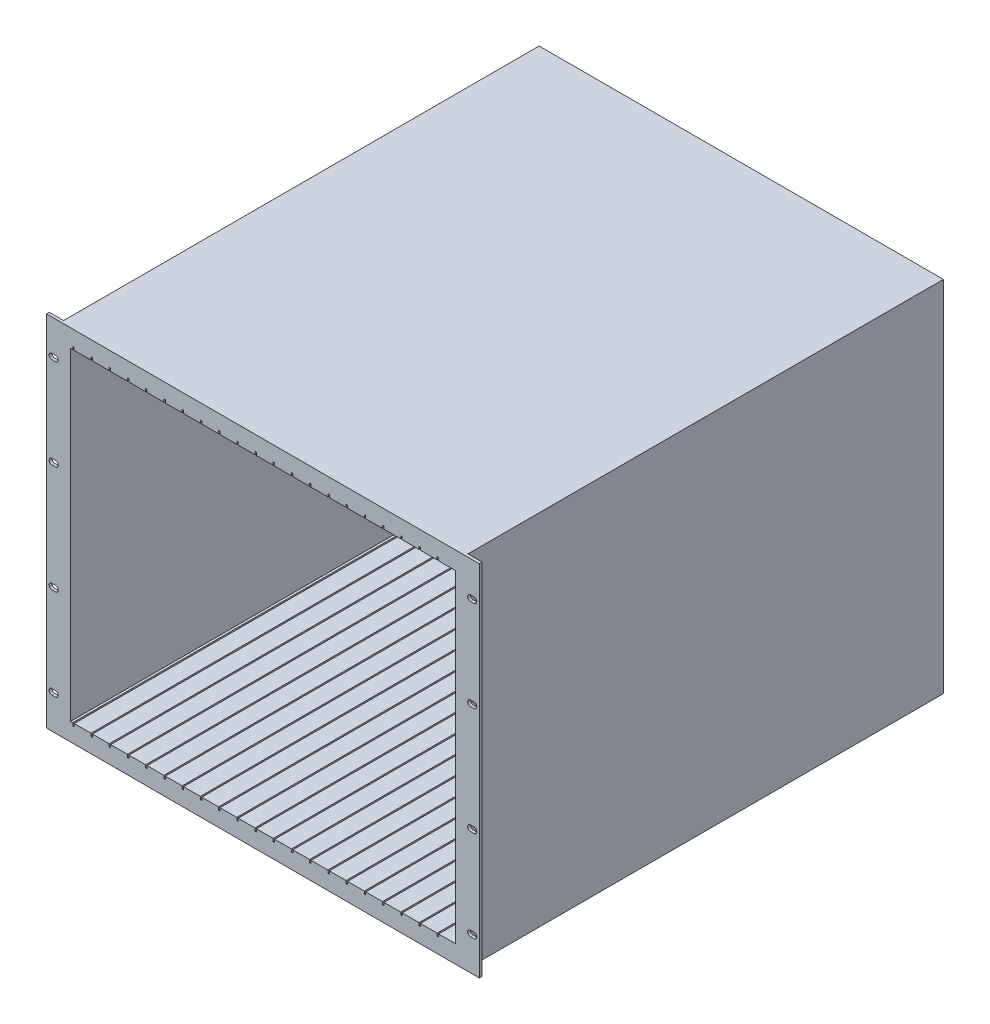
SolidWorks part; units mm, degrees
ref_plane "Front Plane" through (0, 0, 0) normal (0, 0, 1) x (1, 0, 0)
ref_plane "Top Plane" through (0, 0, 0) normal (0, 1, 0) x (1, 0, 0)
ref_plane "Right Plane" through (0, 0, 0) normal (1, 0, 0) x (0, 0, -1)
sketch "Sketch1" plane through (0, 0, 0) normal (0, 1, 0) x (1, 0, 0)
  line L1 (0, 0) -> (482.6, 0)
  line L2 (0, 0) -> (0, 533.4)
  line L3 (0, 533.4) -> (482.6, 533.4)
  line L4 (482.6, 0) -> (482.6, 533.4)
  dimension "D1" = 482.6
  dimension "D2" = 533.4
extrude "Boss-Extrude1" add sketch "Sketch1" along normal blind 19.8374
sketch "Sketch3" plane through (0, 19.8374, 0) normal (0, 1, 0) x (1, 0, 0)
  line L0 (0, 0) -> (482.6, 0) construction
  line L1 (0, 533.4) -> (26.67, 533.4)
  line L2 (0, 533.4) -> (0, 0)
  line L3 (0, 0) -> (26.67, 0)
  line L4 (26.67, 533.4) -> (26.67, 0)
  line L5 (482.6, 533.4) -> (0, 533.4) construction
  line L6 (455.93, 533.4) -> (482.6, 533.4)
  line L7 (455.93, 533.4) -> (455.93, 0)
  line L8 (455.93, 0) -> (482.6, 0)
  line L9 (482.6, 533.4) -> (482.6, 0)
  dimension "D1" = 26.67
  dimension "D2" = 26.67
extrude "Boss-Extrude2" add sketch "Sketch3" along normal blind 180.1876
sketch "Sketch2" plane through (0, 19.8374, 0) normal (0, 1, 0) x (1, 0, 0)
  line L0 (455.93, 533.4) -> (26.67, 533.4) construction
  line L1 (29.21, 533.4) -> (30.7975, 533.4)
  line L2 (29.21, 533.4) -> (29.21, 0)
  line L3 (29.21, 0) -> (30.7975, 0)
  line L4 (30.7975, 533.4) -> (30.7975, 0)
  line L5 (26.67, 0) -> (455.93, 0) construction
  line L6 (49.53, 533.4) -> (51.1175, 533.4)
  line L7 (49.53, 533.4) -> (49.53, 0)
  line L8 (49.53, 0) -> (51.1175, 0)
  line L9 (51.1175, 533.4) -> (51.1175, 0)
  line L10 (69.85, 533.4) -> (71.4375, 533.4)
  line L11 (69.85, 533.4) -> (69.85, 0)
  line L12 (69.85, 0) -> (71.4375, 0)
  line L13 (71.4375, 533.4) -> (71.4375, 0)
  line L14 (90.17, 533.4) -> (91.7575, 533.4)
  line L15 (90.17, 533.4) -> (90.17, 0)
  line L16 (90.17, 0) -> (91.7575, 0)
  line L17 (91.7575, 533.4) -> (91.7575, 0)
  line L18 (110.49, 533.4) -> (112.0775, 533.4)
  line L19 (110.49, 533.4) -> (110.49, 0)
  line L20 (110.49, 0) -> (112.0775, 0)
  line L21 (112.0775, 533.4) -> (112.0775, 0)
  line L22 (130.81, 533.4) -> (132.3975, 533.4)
  line L23 (130.81, 533.4) -> (130.81, 0)
  line L24 (130.81, 0) -> (132.3975, 0)
  line L25 (132.3975, 533.4) -> (132.3975, 0)
  line L26 (151.13, 533.4) -> (152.7175, 533.4)
  line L27 (151.13, 533.4) -> (151.13, 0)
  line L28 (151.13, 0) -> (152.7175, 0)
  line L29 (152.7175, 533.4) -> (152.7175, 0)
  line L30 (171.45, 533.4) -> (173.0375, 533.4)
  line L31 (171.45, 533.4) -> (171.45, 0)
  line L32 (171.45, 0) -> (173.0375, 0)
  line L33 (173.0375, 533.4) -> (173.0375, 0)
  line L34 (191.77, 533.4) -> (193.3575, 533.4)
  line L35 (191.77, 533.4) -> (191.77, 0)
  line L36 (191.77, 0) -> (193.3575, 0)
  line L37 (193.3575, 533.4) -> (193.3575, 0)
  line L38 (212.09, 533.4) -> (213.6775, 533.4)
  line L39 (212.09, 533.4) -> (212.09, 0)
  line L40 (212.09, 0) -> (213.6775, 0)
  line L41 (213.6775, 533.4) -> (213.6775, 0)
  line L42 (232.41, 533.4) -> (233.9975, 533.4)
  line L43 (232.41, 533.4) -> (232.41, 0)
  line L44 (232.41, 0) -> (233.9975, 0)
  line L45 (233.9975, 533.4) -> (233.9975, 0)
  line L46 (252.73, 533.4) -> (254.3175, 533.4)
  line L47 (252.73, 533.4) -> (252.73, 0)
  line L48 (252.73, 0) -> (254.3175, 0)
  line L49 (254.3175, 533.4) -> (254.3175, 0)
  line L50 (273.05, 533.4) -> (274.6375, 533.4)
  line L51 (273.05, 533.4) -> (273.05, 0)
  line L52 (273.05, 0) -> (274.6375, 0)
  line L53 (274.6375, 533.4) -> (274.6375, 0)
  line L54 (293.37, 533.4) -> (294.9575, 533.4)
  line L55 (293.37, 533.4) -> (293.37, 0)
  line L56 (293.37, 0) -> (294.9575, 0)
  line L57 (294.9575, 533.4) -> (294.9575, 0)
  line L58 (313.69, 533.4) -> (315.2775, 533.4)
  line L59 (313.69, 533.4) -> (313.69, 0)
  line L60 (313.69, 0) -> (315.2775, 0)
  line L61 (315.2775, 533.4) -> (315.2775, 0)
  line L62 (334.01, 533.4) -> (335.5975, 533.4)
  line L63 (334.01, 533.4) -> (334.01, 0)
  line L64 (334.01, 0) -> (335.5975, 0)
  line L65 (335.5975, 533.4) -> (335.5975, 0)
  line L66 (354.33, 533.4) -> (355.9175, 533.4)
  line L67 (354.33, 533.4) -> (354.33, 0)
  line L68 (354.33, 0) -> (355.9175, 0)
  line L69 (355.9175, 533.4) -> (355.9175, 0)
  line L70 (374.65, 533.4) -> (376.2375, 533.4)
  line L71 (374.65, 533.4) -> (374.65, 0)
  line L72 (374.65, 0) -> (376.2375, 0)
  line L73 (376.2375, 533.4) -> (376.2375, 0)
  line L74 (394.97, 533.4) -> (396.5575, 533.4)
  line L75 (394.97, 533.4) -> (394.97, 0)
  line L76 (394.97, 0) -> (396.5575, 0)
  line L77 (396.5575, 533.4) -> (396.5575, 0)
  line L78 (415.29, 533.4) -> (416.8775, 533.4)
  line L79 (415.29, 533.4) -> (415.29, 0)
  line L80 (415.29, 0) -> (416.8775, 0)
  line L81 (416.8775, 533.4) -> (416.8775, 0)
  line L83 (435.61, 533.4) -> (437.1975, 533.4)
  line L84 (435.61, 533.4) -> (435.61, 0)
  line L85 (435.61, 0) -> (437.1975, 0)
  line L86 (437.1975, 533.4) -> (437.1975, 0)
  point P8 (30.0038, 533.4)
  point P15 (50.3238, 533.4)
  point P20 (70.6438, 533.4)
  point P25 (90.9637, 533.4)
  point P30 (111.2837, 533.4)
  point P35 (131.6038, 533.4)
  point P40 (151.9237, 533.4)
  point P45 (172.2438, 533.4)
  point P50 (192.5637, 533.4)
  point P55 (212.8838, 533.4)
  point P60 (233.2038, 533.4)
  point P65 (253.5238, 533.4)
  point P70 (273.8438, 533.4)
  point P75 (294.1637, 533.4)
  point P80 (314.4837, 533.4)
  point P85 (334.8038, 533.4)
  point P91 (355.1238, 533.4)
  point P96 (375.4438, 533.4)
  point P101 (395.7638, 533.4)
  point P106 (416.0838, 533.4)
  point P111 (436.4038, 533.4)
  dimension "D1" = 2.54
  dimension "D2" = 1.5875
  dimension "D3" = 21
extrude "Cut-Extrude1" cut sketch "Sketch2" against normal blind 3.175
mirror "Mirror1" about plane through (0, 200.025, 0) normal (0, 1, 0) of bodies 102
sketch "Sketch4" plane through (0, 400.05, 0) normal (0, 1, 0) x (1, 0, 0)
  line L0 (482.6, 533.4) -> (0, 533.4) construction
  line L2 (15.875, 533.4) -> (15.875, 3.175)
  line L4 (466.725, 533.4) -> (466.725, 3.175)
  line L5 (0, 0) -> (482.6, 0) construction
  line L7 (15.875, 3.175) -> (0, 3.175)
  line L8 (15.875, 3.175) -> (15.875, 533.4)
  line L9 (15.875, 533.4) -> (0, 533.4)
  line L10 (0, 3.175) -> (0, 533.4)
  line L11 (482.6, 533.4) -> (466.725, 533.4)
  line L12 (482.6, 533.4) -> (482.6, 3.175)
  line L13 (482.6, 3.175) -> (466.725, 3.175)
  line L14 (466.725, 533.4) -> (466.725, 3.175)
  point P6 (241.3, 3.175)
  point P7 (241.3, 0)
  line M1 (0, 533.4) -> (0, 0)
  line M3 (482.6, 0) -> (482.6, 533.4)
  line M4 (482.6, 533.4) -> (0, 533.4)
  dimension "D1" = 450.85
extrude "Cut-Extrude2" cut sketch "Sketch4" against normal through all contours L7 L2 M4 M1 | L13 L4 M3 M4 region at (7.9375, 400.05, -268.2875) region at (474.6625, 400.05, -268.2875)
hole_wizard "Tap Drill Slot for #10-24 Tap1" positions "Sketch6" profile "Sketch5" size "#10-24" standard "ANSI Inch" slot yes
sketch "Sketch6" plane through (0, 0, 0) normal (0, 0, 1) x (1, 0, 0)
  line L0 (2.8575, 361.95) -> (13.0175, 361.95) construction
  line L1 (241.3, 400.05) -> (241.3, 0) construction
  line L2 (0, 400.05) -> (482.6, 400.05) construction
  line L3 (0, 0) -> (482.6, 0) construction
  line L5 (7.9375, 361.95) -> (7.9375, 14.5824) construction
  point P0 (7.9375, 361.95)
  point P18 (7.9375, 260.35)
  point P20 (7.9375, 139.7)
  point P22 (7.9375, 38.1)
  point P24 (474.6625, 38.1)
  point P25 (474.6625, 139.7)
  point P26 (474.6625, 260.35)
  point P27 (474.6625, 361.95)
  dimension "D1" = 10.16
  dimension "D2" = 38.1
  dimension "D3" = 101.6
  dimension "D4" = 120.65
  dimension "D5" = 101.6
  dimension "D6" = 233.3625
sketch "Sketch5" plane through (7.9375, 361.95, 0) normal (1, 0, 0) x (0, -1, 0)
  line L0 (0, 0) -> (0, 5.0827)
  line L1 (0, 5.0827) -> (3.175, 3.175)
  line L2 (3.175, 3.175) -> (3.175, 0)
  line L5 (3.175, 0) -> (0, 0)
  line L10 (0, 5.0827) -> (-3.175, 3.175) construction
  line L11 (0, -6.35) -> (0, 107.95) construction
  dimension "Hole Dia." = 6.35
  dimension "Hole Depth" = 3.175
  dimension "Drill Angle" = 118
hole_wizard "Tap Drill Slot for #10-24 Tap2" positions "Sketch7" profile "Sketch8" size "#10-24" standard "ANSI Inch" slot yes end condition through all
sketch "Sketch7" plane through (-299.2657, -1361.1684, 25.4) normal (0, 0, 1) x (1, 0, 0)
  line L0 (768.8452, 1723.1184) -> (779.0052, 1723.1184) construction
  point P0 (773.9252, 1723.1184)
sketch "Sketch8" plane through (474.6595, 361.95, 25.4) normal (1, 0, 0) x (0, -1, 0)
  line L0 (0, 0) -> (0, 558.8001)
  line L1 (0, 558.8001) -> (3.175, 558.8001)
  line L2 (3.175, 558.8001) -> (3.175, 0)
  line L3 (3.175, 0) -> (0, 0)
  line L4 (0, -6.35) -> (0, 107.95) construction
  dimension "Thru Hole Dia." = 6.35
  dimension "Thru Hole Depth" = 558.8001
